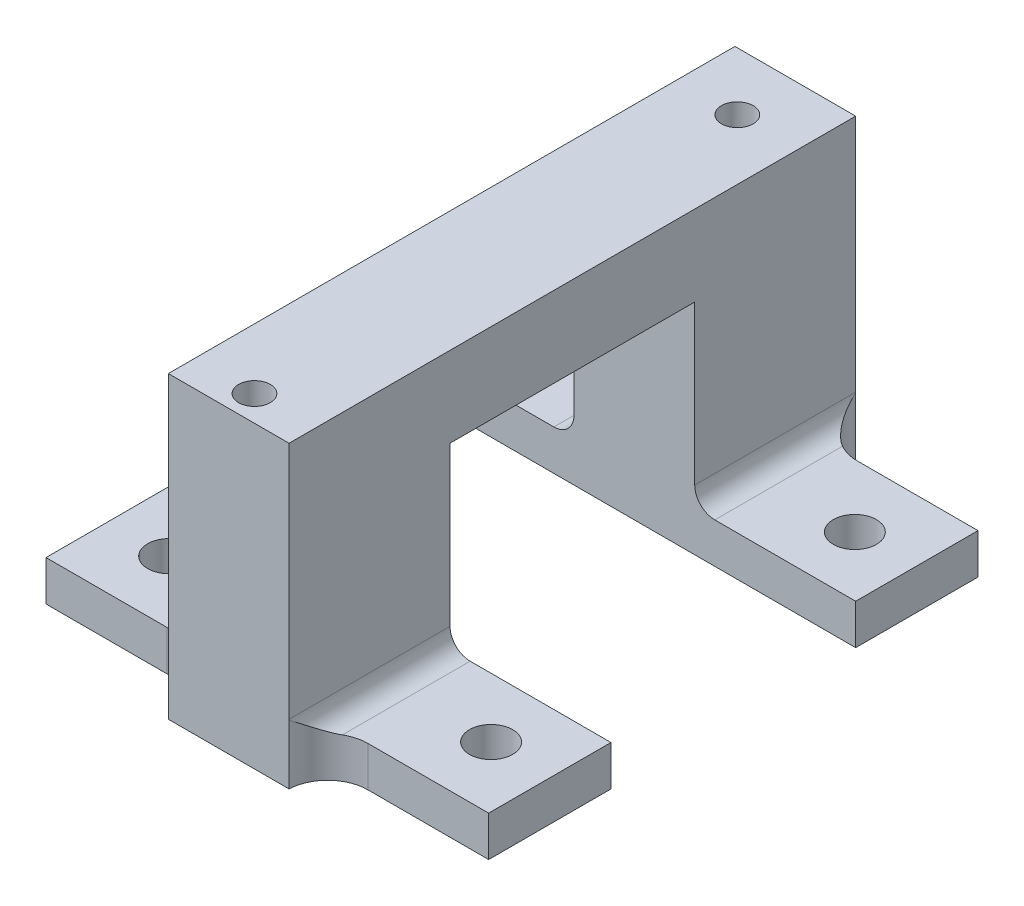
SolidWorks part; units mm, degrees
ref_plane "Front Plane" through (0, 0, 0) normal (0, 0, 1) x (1, 0, 0)
ref_plane "Top Plane" through (0, 0, 0) normal (0, 1, 0) x (1, 0, 0)
ref_plane "Right Plane" through (0, 0, 0) normal (1, 0, 0) x (0, 0, -1)
sketch "Sketch2" plane through (0, 0, 0) normal (1, 0, 0) x (0, 0, -1)
  line L0 (0, 0) -> (0, 24.13) construction
  line L1 (22.352, 23.622) -> (-22.352, 23.622)
  line L2 (-22.352, 23.622) -> (-22.352, 0)
  line L3 (-22.352, 0) -> (-9.652, 0)
  line L4 (-9.652, 0) -> (-9.652, 17.272)
  line L5 (-9.652, 17.272) -> (9.652, 17.272)
  line L6 (9.652, 0) -> (9.652, 17.272)
  line L7 (22.352, 0) -> (9.652, 0)
  line L8 (22.352, 23.622) -> (22.352, 0)
  point P10 (0, 17.272)
  point P13 (0, 23.622)
  dimension "D1" = 9.652
  dimension "D2" = 23.622
  dimension "D3" = 6.35
  dimension "D4" = 12.7
extrude "Boss-Extrude1" add sketch "Sketch2" along normal mid plane 9.525
sketch "Sketch4" plane through (0, 0, 0) normal (0, -1, 0) x (1, 0, 0)
  line L1 (4.7625, 9.652) -> (17.4625, 9.652)
  line L2 (4.7625, 9.652) -> (4.7625, 19.304)
  line L3 (4.7625, 19.304) -> (17.4625, 19.304)
  line L4 (17.4625, 9.652) -> (17.4625, 19.304)
  dimension "D1" = 9.652
  dimension "D2" = 12.7
extrude "Boss-Extrude2" add sketch "Sketch4" against normal blind 3.175
hole_wizard "M3 Clearance Hole1" positions "Sketch5" profile "Sketch7" hole size "M3" standard "ANSI Metric" end condition through all
sketch "Sketch5" plane through (0, 3.175, 0) normal (0, 1, 0) x (1, 0, 0)
  point P0 (12.7, -14.351)
sketch "Sketch7" plane through (12.7, 3.175, 14.351) normal (1, 0, 0) x (0, 0, 1)
  line L0 (0, 0) -> (0, 3.175)
  line L1 (0, 3.175) -> (1.7, 3.175)
  line L2 (1.7, 3.175) -> (1.7, 0)
  line L5 (1.7, 0) -> (0, 0)
  line L11 (0, -6.35) -> (0, 107.95) construction
  dimension "Thru Hole Dia." = 3.4
  dimension "Thru Hole Depth" = 3.175
mirror "Mirror1" about plane through (0, 0, 0) normal (0, 0, 1) of "Boss-Extrude2", "M3 Clearance Hole1"
mirror "Mirror2" about plane through (0, 0, 0) normal (1, 0, 0) of "Boss-Extrude2", "Mirror1", "M3 Clearance Hole1"
fillet "Fillet1" radius 3.175 4 edges at (-4.7625, 1.5875, -19.304) (4.7625, 1.5875, -19.304) (4.7625, 1.5875, 19.304) (-4.7625, 1.5875, 19.304)
fillet "Fillet2" radius 1.5875 4 edges at (4.7625, 3.175, 16.002) (4.7625, 3.175, -16.002) (-4.7625, 3.175, -16.002) (-4.7625, 3.175, 16.002)
hole_wizard "Tap Drill for M3x0.5 Tap1" positions "Sketch8" profile "Sketch9" hole size "M3x0.5" standard "ANSI Metric" end condition through all
sketch "Sketch8" plane through (0, 23.622, 0) normal (0, 1, 0) x (1, 0, 0)
  point P0 (0, 17.779)
  point P3 (0, -20.321)
sketch "Sketch9" plane through (0, 23.622, -17.779) normal (1, 0, 0) x (0, 0, 1)
  line L0 (0, 0) -> (0, 23.622)
  line L1 (0, 23.622) -> (1.25, 23.622)
  line L2 (1.25, 23.622) -> (1.25, 0)
  line L5 (1.25, 0) -> (0, 0)
  line L11 (0, -6.35) -> (0, 107.95) construction
  dimension "Thru Hole Dia." = 2.5
  dimension "Thru Hole Depth" = 23.622
